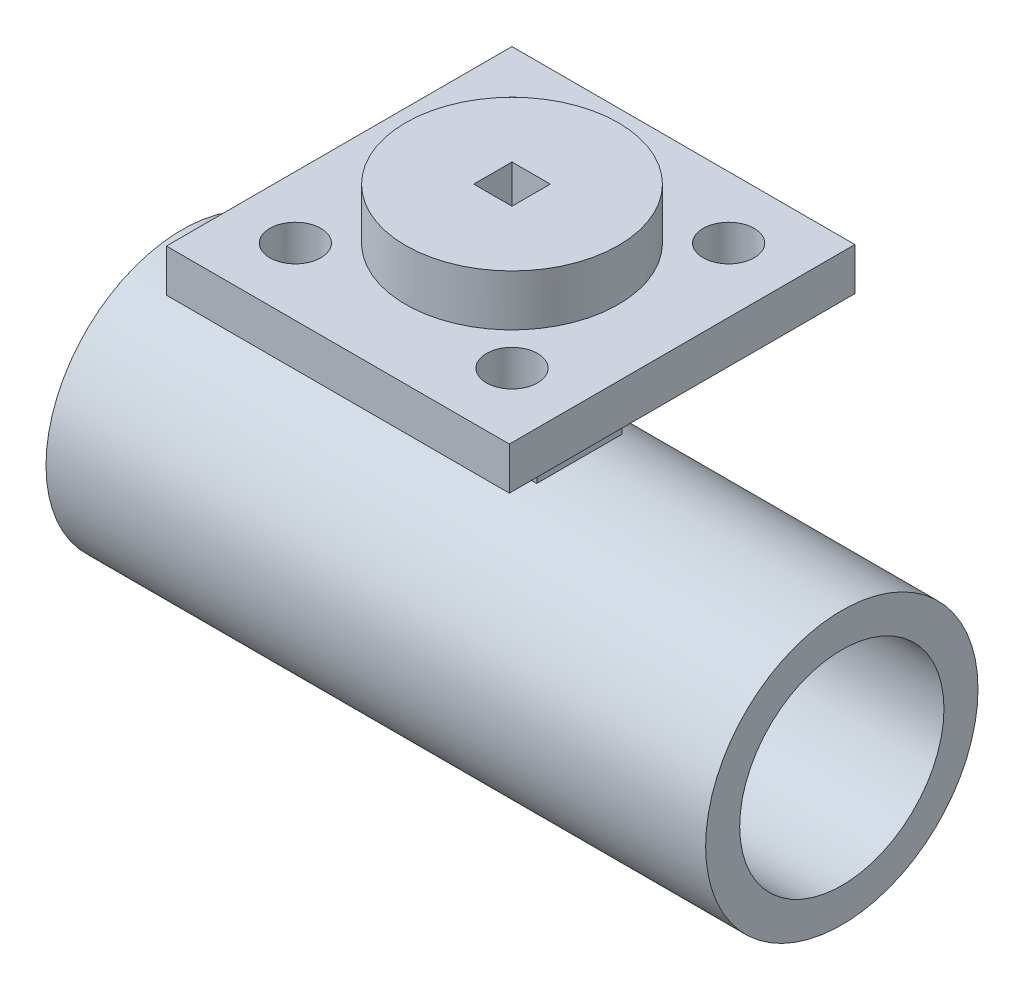
SolidWorks part; units mm, degrees
material "Brass"
ref_plane "Płaszczyzna przednia" through (0, 0, 0) normal (0, 0, 1) x (1, 0, 0)
ref_plane "Płaszczyzna górna" through (0, 0, 0) normal (0, 1, 0) x (1, 0, 0)
ref_plane "Płaszczyzna prawa" through (0, 0, 0) normal (1, 0, 0) x (0, 0, -1)
sketch "Szkic1" plane through (0, 0, 0) normal (0, 0, 1) x (1, 0, 0)
  line L0 (0, 0) -> (77.5, 0)
  line L1 (0, 0) -> (0, 12)
  line L2 (77.5, 0) -> (77.5, 12)
  line L3 (38.75, 0) -> (38.75, 34)
  line L4 (38.75, 34) -> (22.75, 34)
  line L5 (38.75, 34) -> (54.75, 34)
  line L6 (22.75, 34) -> (22.75, 29)
  line L7 (22.75, 29) -> (54.75, 29)
  line L8 (54.75, 29) -> (54.75, 34)
  line L9 (38.75, 29) -> (30.8336, 29)
  line L10 (0, 12) -> (0, 16)
  line L11 (0, 16) -> (77.5, 16)
  line L12 (77.5, 16) -> (77.5, 12)
  line L13 (77.5, 12) -> (0, 12)
  line L14 (30.8336, 29) -> (30.8336, 16)
  line L15 (46.6664, 29) -> (46.6664, 16)
extrude "Dodanie-wyciągnięcie1" add sketch "Szkic1" along normal blind 16 and the other way blind 16 contours L15 L7 L3 L11 | L7 L14 L11 L3 | L6 L7 L3 L4 | L7 L8 L5 L3 region at (34.7918, 22.5, 0) region at (42.7082, 22.5, 0) region at (30.75, 31.5, 0) region at (46.75, 31.5, 0)
sketch "Szkic2" plane through (0, 34, 0) normal (0, 1, 0) x (1, 0, 0)
  line L0 (38.75, 16) -> (38.75, 0)
  line L1 (38.75, 0) -> (51.4779, 12.7279)
  line L2 (22.75, 16) -> (54.75, 16) construction
  circle A0 centre (51.4779, 12.7279) radius 3
  circle A1 centre (38.75, 0) radius 18
  circle A2 centre (38.75, 0) radius 18
  circle A3 centre (51.4779, -12.7279) radius 3
  circle A4 centre (38.75, 0) radius 18
  circle A5 centre (26.0221, -12.7279) radius 3
  circle A6 centre (38.75, 0) radius 18
  circle A7 centre (26.0221, 12.7279) radius 3
  point P19 (38.75, 0)
  dimension "D1" = 4
extrude "Wytnij-wyciągnięcie1" cut sketch "Szkic2" against normal blind 15 contours A6 A7 | A6 A7 | A1 A0 | L1 A1 A0 | A0 A1 L1 | A2 A3 | A2 A3 | A4 A5 | A4 A5 region at (49.6715, 34, -12.6715) region at (51.4215, 34, -10.9215) region at (52.3456, 34, -13.5956) region at (26.9535, 34, -11.7965) region at (25.1544, 34, -13.5956) region at (52.3456, 34, 13.5956) region at (50.5465, 34, 11.7965) region at (26.9535, 34, 11.7965) region at (25.1544, 34, 13.5956)
sketch "Szkic3" plane through (0, 34, 0) normal (0, 1, 0) x (1, 0, 0)
  line L0 (38.75, 16) -> (38.75, 0)
  line L1 (22.75, 16) -> (54.75, 16) construction
  line L3 (36.5, -2.2497) -> (41, -2.2497)
  line L4 (36.5, -2.2497) -> (36.5, 2.2497)
  line L5 (36.5, 2.2497) -> (41, 2.2497)
  line L6 (41, -2.2497) -> (41, 2.2497)
  line L7 (36.5, -2.2497) -> (41, 2.2497) construction
  line L8 (36.5, 2.2497) -> (41, -2.2497) construction
  circle A0 centre (38.75, 0) radius 12.5
extrude "Dodanie-wyciągnięcie2" add sketch "Szkic3" along normal blind 6 contours L3 L6 L5 L4 | A0 region at (39.875, 34, -2.1861)
sketch "Szkic4" plane through (0, 0, 0) normal (0, 0, 1) x (1, 0, 0)
  line L0 (0, 0) -> (77.5, 0)
  line L1 (77.5, 0) -> (77.5, 12)
  line L2 (77.5, 12) -> (0, 12)
  line L3 (0, 12) -> (0, 0)
  line L4 (0, 12) -> (0, 16)
  line L5 (0, 16) -> (30.8336, 16)
  line L6 (46.6664, 16) -> (77.5, 16)
  line L7 (77.5, 16) -> (77.5, 12)
  line L8 (30.8336, 16) -> (46.6664, 16)
revolve "Obrót2" add sketch "Szkic4" angle 360 about L0 region at (38.75, 14, 0)
sketch "Szkic5" plane through (0, 0, 16) normal (0, 0, 1) x (1, 0, 0)
  line L0 (46.6664, 29) -> (46.6664, 16) construction
  line L1 (30.8336, 16) -> (46.6664, 16)
  line L2 (30.8336, 16) -> (30.8336, 29)
  line L3 (30.8336, 29) -> (46.6664, 29)
  line L4 (46.6664, 16) -> (46.6664, 29)
  line L5 (46.6664, 29) -> (54.75, 29) construction
extrude "Wytnij-wyciągnięcie2" cut sketch "Szkic5" against normal blind 11
sketch "Szkic6" plane through (0, 0, -16) normal (0, 0, -1) x (-1, 0, 0)
  line L1 (-46.6664, 16) -> (-30.8336, 16)
  line L2 (-46.6664, 16) -> (-46.6664, 29)
  line L3 (-46.6664, 29) -> (-30.8336, 29)
  line L4 (-30.8336, 16) -> (-30.8336, 29)
extrude "Wytnij-wyciągnięcie3" cut sketch "Szkic6" against normal blind 11
sketch "Szkic7" plane through (0, 34, 0) normal (0, 1, 0) x (1, 0, 0)
  line L1 (22.75, 16) -> (18.7499, 16)
  line L2 (22.75, 16) -> (22.75, 19.9925)
  line L3 (22.75, 19.9925) -> (18.7499, 19.9925)
  line L4 (18.7499, 16) -> (18.7499, 19.9925)
  line L5 (18.7499, 19.9925) -> (59.0416, 19.9925)
  line L6 (18.7499, 19.9925) -> (18.7499, -20.6022)
  line L7 (18.7499, -20.6022) -> (59.0416, -20.6022)
  line L8 (59.0416, 19.9925) -> (59.0416, -20.6022)
  line M1 (22.75, 16) -> (22.75, -16)
  line M2 (22.75, -16) -> (54.75, -16)
  line M3 (54.75, -16) -> (54.75, 16)
  line M4 (54.75, 16) -> (22.75, 16)
extrude "Dodanie-wyciągnięcie3" add sketch "Szkic7" against normal blind 5 contours L8 L5 L2 L1 L6 L7 M4 M3 M2 M1 | L4 L1 L2 L3 region at (23.322, 34, -17.9962) region at (20.7499, 34, -17.9962)
